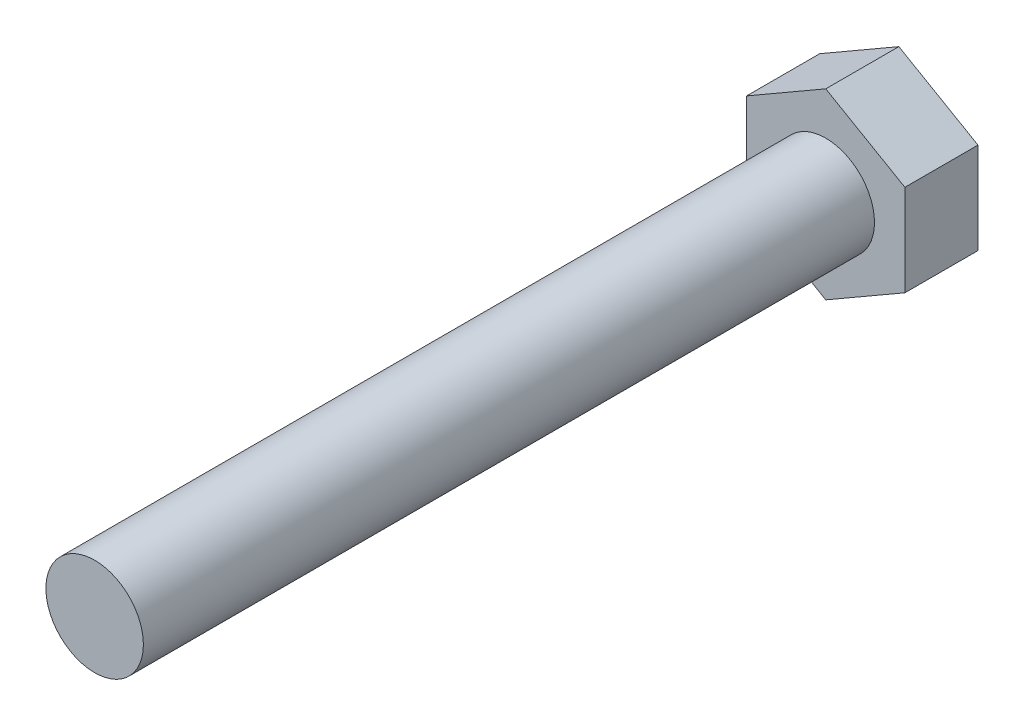
SolidWorks part; units mm, degrees
ref_plane "Front Plane" through (0, 0, 0) normal (0, 0, 1) x (1, 0, 0)
ref_plane "Top Plane" through (0, 0, 0) normal (0, 1, 0) x (1, 0, 0)
ref_plane "Right Plane" through (0, 0, 0) normal (1, 0, 0) x (0, 0, -1)
sketch "Sketch1" plane through (0, 0, 0) normal (0, 0, 1) x (1, 0, 0)
  line L1 (0, 7.5) -> (-6.4952, 3.75)
  line L2 (-6.4952, 3.75) -> (-6.4952, -3.75)
  line L3 (-6.4952, -3.75) -> (0, -7.5)
  line L4 (0, -7.5) -> (6.4952, -3.75)
  line L5 (6.4952, -3.75) -> (6.4952, 3.75)
  line L6 (6.4952, 3.75) -> (0, 7.5)
  circle A0 centre (0, 0) radius 7.5 construction
  dimension "D1" = 15
extrude "Boss-Extrude1" add sketch "Sketch1" along normal blind 6
sketch "Sketch2" plane through (0, 0, 6) normal (0, 0, 1) x (1, 0, 0)
  circle A0 centre (0, 0) radius 4
  dimension "D1" = 8
extrude "Longitud de tornilllo" add sketch "Sketch2" along normal blind 60
sketch "Sketch3" plane through (0, 0, 66) normal (0, 0, 1) x (1, 0, 0)
  circle A0 centre (0, 0) radius 4
curve "Espiral" pitch 0.75 height 50 turns 66.6667
ref_plane "Plane1" through (-4, 0, 66) normal (0, 0.9996, -0.0298) x (1, 0, 0)
sketch "Sketch4" plane through (-4, 0, 66) normal (0, 0.9996, -0.0298) x (1, 0, 0)
  line L0 (0, 0.25) -> (0, -0.25)
  line L3 (0, 59.9733) -> (0, 0) construction
  line L4 (0, 0.25) -> (0.5, -0.001)
  line L5 (0.5, -0.001) -> (0, -0.25)
  ellipse E0 centre (4, 0) end of major axis (0, 0) minor radius 0.1193 construction
  point P7 (0, 0)
  dimension "D1" = 0.5
  dimension "D2" = 0.5
sweep "Cut-Sweep1" [suppressed] cut profiles "Sketch4" path "Espiral"
